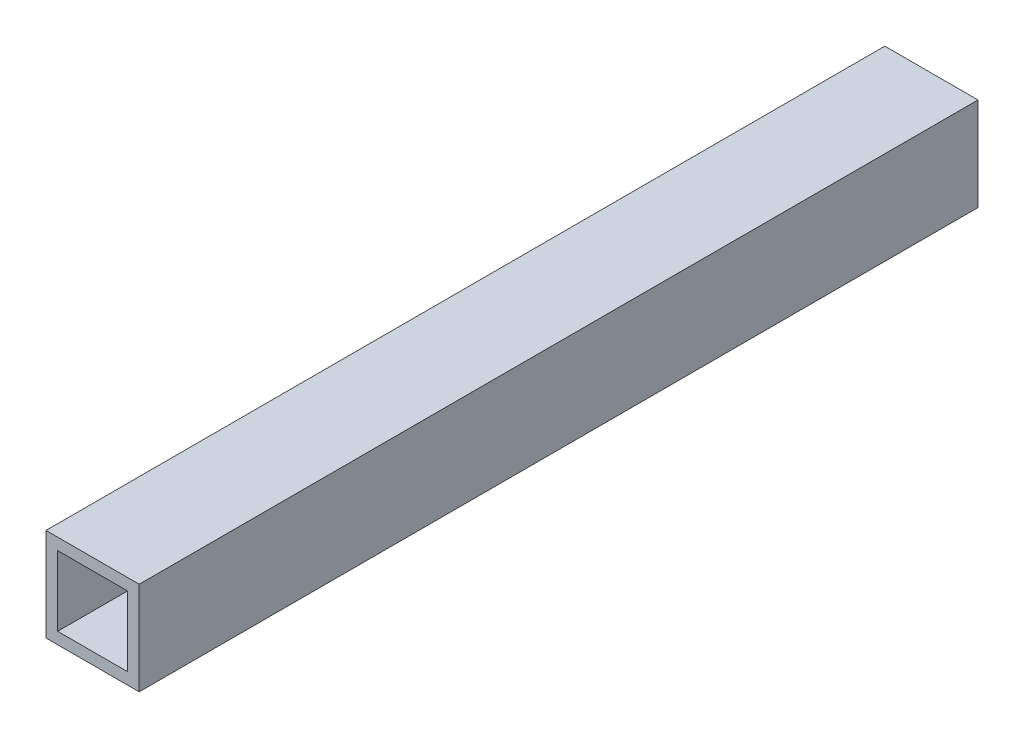
SolidWorks part; units mm, degrees
material "6061 Alloy"
ref_plane "Front Plane" through (0, 0, 0) normal (0, 0, 1) x (1, 0, 0)
ref_plane "Top Plane" through (0, 0, 0) normal (0, 1, 0) x (1, 0, 0)
ref_plane "Right Plane" through (0, 0, 0) normal (1, 0, 0) x (0, 0, -1)
sketch "Sketch1" plane through (0, 0, 0) normal (0, 0, 1) x (1, 0, 0)
  line L0 (12.7, 0) -> (9.525, 0) construction
  line L1 (-12.7, 0) -> (12.7, 0) construction
  line L2 (0, 12.7) -> (0, -12.7)
  point P7 (0, 0)
sketch "Sketch2" plane through (0, 0, 0) normal (1, 0, 0) x (0, 0, -1)
  line L0 (114.3, 0) -> (-114.3, 0)
  point P4 (0, 0)
  dimension "Length" = 228.6
sketch "Sketch3" plane through (0, 0, 0) normal (0, 0, 1) x (1, 0, 0)
  line L0 (-12.7, 0) -> (12.7, 0) construction
  line L5 (12.7, -12.7) -> (-12.7, -12.7)
  line L6 (12.7, -12.7) -> (12.7, 12.7)
  line L11 (12.7, 12.7) -> (-12.7, 12.7)
  line L12 (-12.7, -12.7) -> (-12.7, 12.7)
  line L14 (12.7, -12.7) -> (-12.7, 12.7) construction
  line L15 (12.7, 12.7) -> (-12.7, -12.7) construction
  line L16 (9.525, -9.525) -> (-9.525, -9.525)
  line L17 (9.525, -9.525) -> (9.525, 9.525)
  line L18 (9.525, 9.525) -> (-9.525, 9.525)
  line L19 (-9.525, -9.525) -> (-9.525, 9.525)
  line L20 (9.525, -9.525) -> (-9.525, 9.525) construction
  line L21 (9.525, 9.525) -> (-9.525, -9.525) construction
  point P0 (0, 0)
  point P5 (0, 0)
  point P13 (9.525, -12.7)
  dimension "D1" = 3.175
extrude "Boss-Extrude1" add sketch "Sketch3" along normal up to vertex (114.3 mm away) and the other way up to vertex (114.3 mm away) up to point (0, 0, 114.3) other way up to point (0, 0, -114.3)
sketch "Sketch5" plane through (0, 0, 0) normal (1, 0, 0) x (0, 0, -1)
  line L0 (-114.3, 0) -> (114.3, 0) construction
  line L3 (-114.3, -12.7) -> (-114.3, 12.7) construction
  line L4 (114.3, -12.7) -> (114.3, 12.7) construction
  point P6 (-85.725, 0)
  point P7 (-76.2, 0)
  point P8 (76.2, 0)
  point P10 (85.725, 0)
  dimension "D1" = 28.575
  dimension "D2" = 38.1
  dimension "D3" = 28.575
  dimension "D4" = 38.1
equation "\"D1@Sketch3\"=\"Wall thickness@Sketch1\""
equation "\"D1@Sketch5\"=\"Width@Sketch1\"*1.125"
equation "\"D2@Sketch5\"=\"Width@Sketch1\"*1.5"
equation "\"D3@Sketch5\"=\"D1@Sketch5\""
equation "\"D4@Sketch5\"=\"D2@Sketch5\""
equation "\"D2@Sketch3\"=\"Wall Thickness@Sketch1\""
